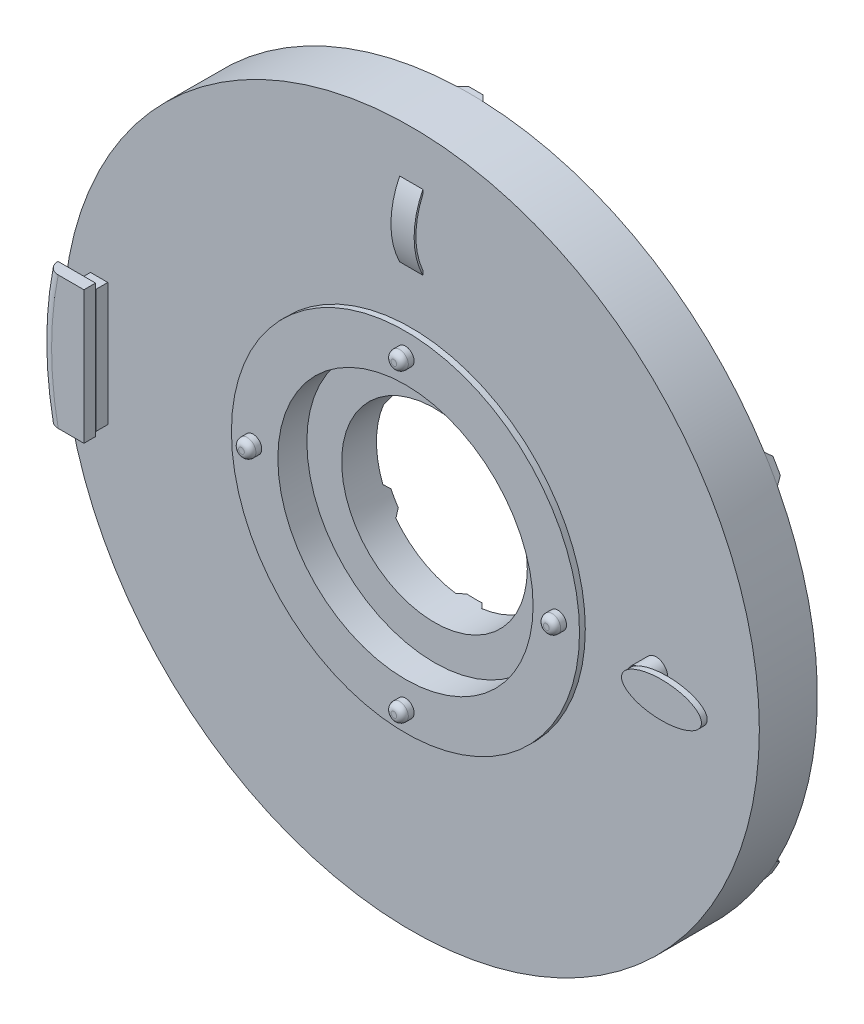
SolidWorks part; units mm, degrees
ref_plane "Front Plane" through (0, 0, 0) normal (0, 0, 1) x (1, 0, 0)
ref_plane "Top Plane" through (0, 0, 0) normal (0, 1, 0) x (1, 0, 0)
ref_plane "Right Plane" through (0, 0, 0) normal (1, 0, 0) x (0, 0, -1)
sketch "Sketch1" plane through (0, 0, 0) normal (0, 0, 1) x (1, 0, 0)
  circle A0 centre (0, 0) radius 600
extrude "Boss-Extrude1" add sketch "Sketch1" along normal blind 100
sketch "Sketch2" plane through (0, 0, 100) normal (0, 0, 1) x (1, 0, 0)
  circle A0 centre (0, 0) radius 300
extrude "Boss-Extrude2" add sketch "Sketch2" along normal blind 10
sketch "Sketch3" plane through (0, 0, 110) normal (0, 0, 1) x (1, 0, 0)
  circle A0 centre (0, 0) radius 220
extrude "Cut-Extrude1" cut sketch "Sketch3" against normal blind 50
sketch "Sketch4" plane through (0, 0, 60) normal (0, 0, 1) x (1, 0, 0)
  circle A0 centre (0, 0) radius 160
extrude "Cut-Extrude2" cut sketch "Sketch4" against normal through all
sketch "Sketch6" plane through (0, 0, 110) normal (0, 0, 1) x (1, 0, 0)
  circle A0 centre (-262.6987, 0) radius 14.913
  circle A1 centre (0, 262.6987) radius 14.913
  circle A2 centre (262.6987, 0) radius 14.913
  circle A3 centre (0, -262.6987) radius 14.913
  dimension "D1" = 4
extrude "Boss-Extrude4" add sketch "Sketch6" along normal blind 20
fillet "Fillet1" radius 10 4 edges at (-247.7856, 0, 130) (14.913, -262.6987, 130) (277.6117, 0, 130) (14.913, 262.6987, 130)
sketch "Sketch7" plane through (0, 0, 100) normal (0, 0, 1) x (1, 0, 0)
  line L0 (-552.9291, -106.1119) -> (-552.9291, 106.1119)
  line L5 (-552.9291, 106.1119) -> (-523.103, 106.1119)
  line L6 (-523.103, 106.1119) -> (-523.103, -106.1119)
  line L7 (0, 0) -> (-640.1129, 0) construction
  line L8 (-552.9291, -106.1119) -> (-523.103, -106.1119)
  point P8 (-523.103, 0)
  point P9 (-552.9291, 0)
extrude "Boss-Extrude5" add sketch "Sketch7" along normal blind 20
sketch "Sketch9" plane through (0, 0, 120) normal (0, 0, 1) x (1, 0, 0)
  line L0 (0, 0) -> (-671.0861, 0) construction
  line L1 (-588.9494, 114.6235) -> (-524.2502, 114.6235)
  line L2 (-524.2502, 114.6235) -> (-524.2502, -114.6235)
  line L3 (-524.2502, -114.6235) -> (-588.9494, -114.6235)
  arc A0 (-588.9494, -114.6235) -> (-588.9494, 114.6235) centre (0, 0) cw
extrude "Boss-Extrude6" add sketch "Sketch9" along normal blind 20
fillet "Fillet2" radius 20 1 edges at (-600, 0, 140)
sketch "Sketch10" plane through (0, 0, 100) normal (0, 0, 1) x (1, 0, 0)
  circle A0 centre (422.1533, 0) radius 19.778
extrude "Boss-Extrude7" add sketch "Sketch10" along normal blind 30
sketch "Sketch11" plane through (0, 0, 130) normal (0, 0, 1) x (1, 0, 0)
  circle A1 centre (422.1533, 0) radius 19.778 construction
  ellipse E0 centre (471.276, 0) end of major axis (402.3753, 0) minor radius 30.6148
extrude "Boss-Extrude9" add sketch "Sketch11" along normal blind 10
sketch "Sketch12" plane through (0, 0, 0) normal (1, 0, 0) x (0, 0, -1)
  line L1 (-100, 600) -> (-100, -600) construction
  line L2 (-100, 509.4377) -> (-100, 516.6099)
  line L3 (-100, 395.5793) -> (-100, 388.4071)
  arc A0 (-100, 509.4377) -> (-100, 395.5793) centre (28.631, 452.5085) ccw
  arc A1 (-100, 516.6099) -> (-100, 388.4071) centre (28.631, 452.5085) ccw
extrude "Boss-Extrude10" add sketch "Sketch12" along normal blind 20
mirror "Mirror1" about plane through (0, 0, 0) normal (1, 0, 0) of "Boss-Extrude10"
sketch "Sketch13" plane through (0, 0, 0) normal (0, 0, -1) x (-1, 0, 0)
  line L1 (20.6208, 158.6656) -> (20.6208, 599.6455)
  line L3 (-22.8675, 158.3574) -> (-22.8675, 599.5641)
  line L4 (-22.8675, 599.5641) -> (20.6208, 599.6455)
  circle A0 centre (0, 0) radius 160 construction
  arc A2 (-22.8675, 158.3574) -> (20.6208, 158.6656) centre (0, 0) cw
  circle A3 centre (0, 0) radius 600 construction
extrude "Boss-Extrude11" add sketch "Sketch13" along normal blind 10
chamfer "Chamfer1" distance 9.0254 angle 45 2 edges at (-20.6208, 379.1556, -10) (22.8675, 378.9608, -10) tangent propagation no
pattern_circular "CirPattern1" count 6 over 360 about axis through (0, 0, 0) along (0, 0, 1) of "Boss-Extrude11", "Chamfer1" reverse direction yes
sketch "Sketch14" plane through (0, 0, 0) normal (0, 0, -1) x (-1, 0, 0)
  circle A0 centre (-195.0165, 0) radius 17.4447
  circle A1 centre (-97.5082, 168.8892) radius 17.4447
  circle A2 centre (97.5082, 168.8892) radius 17.4447
  circle A3 centre (195.0165, 0) radius 17.4447
  circle A4 centre (97.5082, -168.8892) radius 17.4447
  circle A5 centre (-97.5082, -168.8892) radius 17.4447
  dimension "D1" = 6
extrude "Boss-Extrude12" add sketch "Sketch14" along normal blind 10
fillet "Fillet3" radius 8 6 edges at (80.0636, 168.8892, -10) (80.0636, -168.8892, -10) (-114.9529, -168.8892, -10) (-212.4612, 0, -10) (-114.9529, 168.8892, -10) (177.5718, 0, -10)
